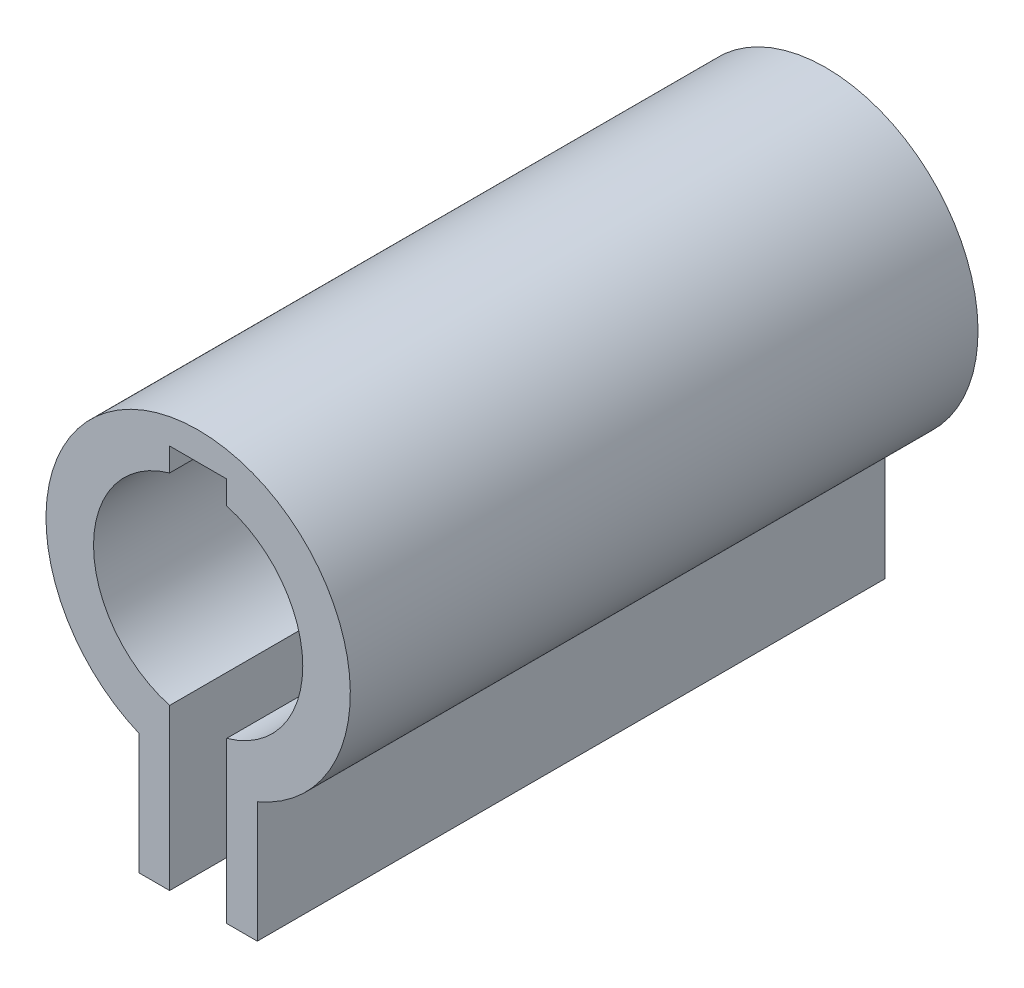
SolidWorks part; units mm, degrees
ref_plane "Front Plane" through (0, 0, 0) normal (0, 0, 1) x (1, 0, 0)
ref_plane "Top Plane" through (0, 0, 0) normal (0, 1, 0) x (1, 0, 0)
ref_plane "Right Plane" through (0, 0, 0) normal (1, 0, 0) x (0, 0, -1)
sketch "Sketch1" plane through (0, 0, 0) normal (0, 0, 1) x (1, 0, 0)
  circle A0 centre (0, 0) radius 11
  circle A1 centre (0, 0) radius 16
  dimension "D1" = 22
  dimension "D2" = 5
extrude "Boss-Extrude1" add sketch "Sketch1" along normal blind 33 and the other way blind 33
sketch "Sketch2" plane through (0, 0, 33) normal (0, 0, 1) x (1, 0, 0)
  line L0 (-3, 10.5402) -> (-3, 13.0402)
  line L2 (3, 13.0402) -> (3, 10.5402)
  line L3 (0, 0) -> (0, 13.0402) construction
  line L4 (-3, 13.0402) -> (0, 13.0402)
  line L5 (0, 13.0402) -> (3, 13.0402)
  line L6 (0, 0) -> (-3, 10.5402) construction
  line L7 (0, 0) -> (3, 10.5402) construction
  arc A0 (-3, 10.5402) -> (3, 10.5402) centre (0, 0) cw
  dimension "D1" = 3
  dimension "D2" = 3
  dimension "D3" = 2.5
extrude "Cut-Extrude1" cut sketch "Sketch2" against normal blind 33
mirror "Mirror2" about plane through (0, 0, 0) normal (0, 0, -1) of "Cut-Extrude1"
sketch "Sketch3" plane through (0, 0, 33) normal (0, 0, 1) x (1, 0, 0)
  line L0 (-3, -10.583) -> (-3, -15.7162)
  line L1 (-3, -15.7162) -> (-3, -10.583)
  line L2 (3, -10.583) -> (3, -15.7162)
  line L3 (-3, -10.583) -> (3, -10.583)
  line L4 (-3, -15.7162) -> (-3, -27.4422)
  line L5 (-3, -27.4422) -> (-6.2184, -27.4422)
  line L6 (-6.2184, -27.4422) -> (-6.2184, -14.7422)
  line L7 (-6.2184, -14.7422) -> (-3, -14.7422)
  line L8 (3, -15.7162) -> (3, -27.4422)
  line L9 (3, -27.4422) -> (6.2184, -27.4422)
  line L10 (6.2184, -27.4422) -> (6.2184, -14.7422)
  line L11 (6.2184, -14.7422) -> (3, -14.7422)
  arc A0 (-3, 10.583) -> (3, 10.583) centre (0, 0) ccw construction
  circle A1 centre (0, 0) radius 16 construction
  circle M6 centre (0, 0) radius 16
  dimension "D1" = 12.7
extrude "Boss-Extrude2" add sketch "Sketch3" against normal through all contours L6 L5 L4 M6 | L9 L10 L8 M6 region at (-4.6307, -21.3633, 33) region at (4.6307, -21.3633, 33)
sketch "Sketch4" plane through (0, 0, 33) normal (0, 0, 1) x (1, 0, 0)
  line L0 (-3, -10.583) -> (-3, -16.2715)
  line L1 (-3, -10.583) -> (3, -10.583)
  line L2 (3, -10.583) -> (3, -15.7162)
  line L3 (-3, -15.7162) -> (-3, -27.4422) construction
  line L4 (-3, -16.2715) -> (3, -16.2715)
  line L5 (3, -15.7162) -> (3, -27.4422) construction
  line L6 (3, -16.2715) -> (3, -15.7162)
  arc A0 (-3, 10.583) -> (3, 10.583) centre (0, 0) ccw construction
extrude "Cut-Extrude4" cut sketch "Sketch4" against normal through all
